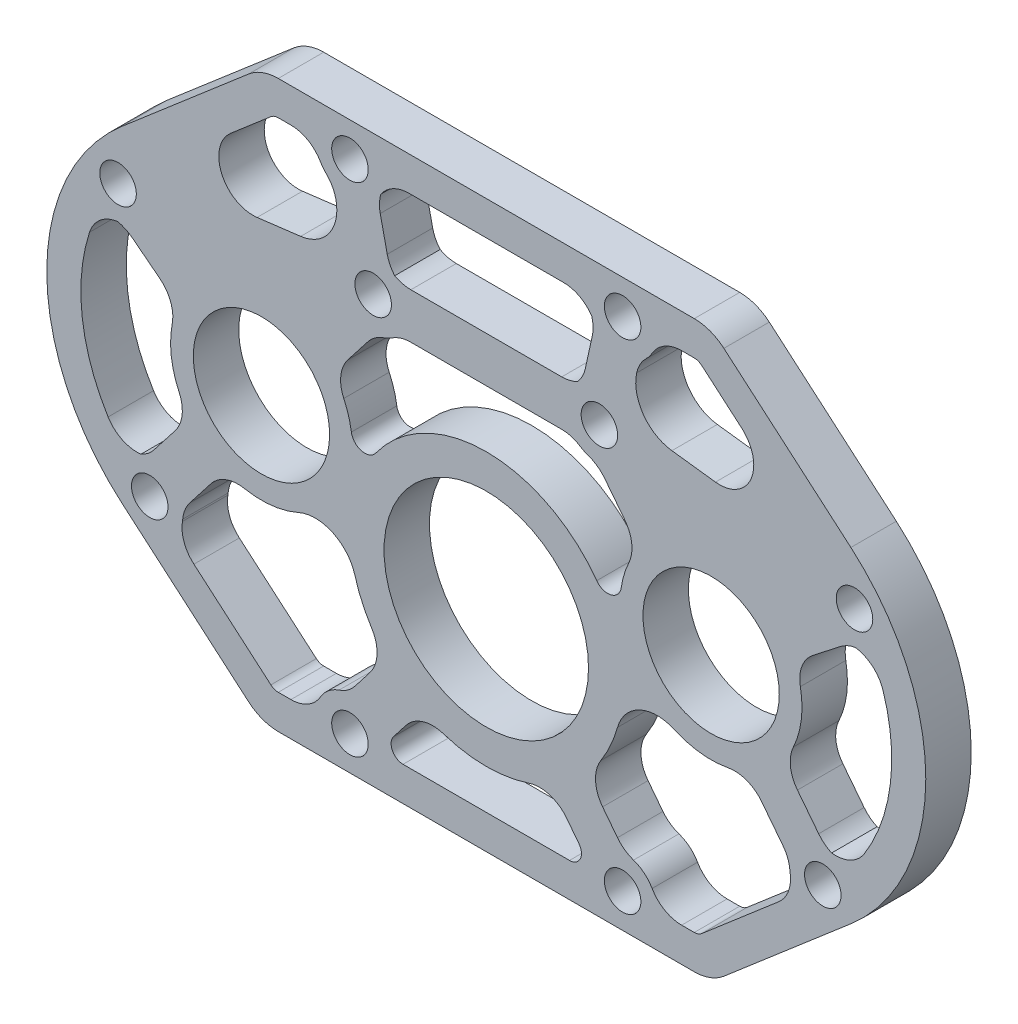
SolidWorks part; units mm, degrees
material "6061-T6 (SS)"
ref_plane "Front Plane" through (0, 0, 0) normal (0, 0, 1) x (1, 0, 0)
ref_plane "Top Plane" through (0, 0, 0) normal (0, 1, 0) x (1, 0, 0)
ref_plane "Right Plane" through (0, 0, 0) normal (1, 0, 0) x (0, 0, -1)
sketch "Sketch1" plane through (0, 0, 0) normal (0, 0, 1) x (1, 0, 0)
  line L0 (127, 25.4) -> (127, 0) construction
  line L1 (0, 0) -> (254, 0)
  line L2 (0, 0) -> (0, 25.4)
  line L3 (0, 25.4) -> (254, 25.4)
  line L4 (254, 0) -> (254, 25.4)
  line L18 (110.6338, 19.05) -> (106.9677, 12.7)
  line L19 (106.9677, 12.7) -> (110.6338, 6.35)
  line L20 (110.6338, 6.35) -> (117.9662, 6.35)
  line L21 (117.9662, 6.35) -> (121.6323, 12.7)
  line L22 (121.6323, 12.7) -> (117.9662, 19.05)
  line L23 (117.9662, 19.05) -> (110.6338, 19.05)
  circle A0 centre (82.8819, 22.86) radius 30 construction
  circle A1 centre (145.7181, 22.86) radius 30 construction
  circle A2 centre (82.8819, 22.86) radius 7.62 construction
  circle A3 centre (145.7181, 22.86) radius 8.636
  circle A4 centre (82.8819, 22.86) radius 8.636
  circle A5 centre (145.7181, 22.86) radius 7.62 construction
  circle A6 centre (114.3, 12.7) radius 25.4 construction
  circle A7 centre (114.3, 12.7) radius 26.67
  circle A8 centre (114.3, 12.7) radius 22.2377 construction
  circle A11 centre (114.3, 12.7) radius 6.35 construction
  dimension "D4" = 17.272
  dimension "D9" = 53.34
  dimension "D13" = 12.7
  dimension "D1" = 25.4
  dimension "D2" = 254
  dimension "D10" = 12.7
  dimension "D12" = 12.7
  dimension "D14" = 10.16
sketch "Sketch3" plane through (0, 0, 0) normal (0, 0, 1) x (1, 0, 0)
  line L0 (82.8819, 52.86) -> (145.7181, 52.86) construction
  line L5 (82.8819, -7.14) -> (145.7181, -7.14) construction
  line L6 (82.8819, 22.86) -> (98.4918, 42.8972) construction
  line L9 (114.3, 52.86) -> (114.3, -16.665) construction
  line L10 (63.3497, 45.6304) -> (82.8819, 62.385)
  line L25 (82.8819, 62.385) -> (145.7181, 62.385)
  line L26 (145.7181, 62.385) -> (165.2503, 45.6304)
  line L27 (110.6338, 19.05) -> (106.9677, 12.7)
  line L28 (106.9677, 12.7) -> (110.6338, 6.35)
  line L29 (110.6338, 6.35) -> (117.9662, 6.35)
  line L30 (117.9662, 6.35) -> (121.6323, 12.7)
  line L31 (121.6323, 12.7) -> (117.9662, 19.05)
  line L32 (117.9662, 19.05) -> (110.6338, 19.05)
  line L33 (110.565, 18.9308) -> (106.9677, 12.7)
  line L34 (106.9677, 12.7) -> (110.6338, 6.35)
  line L35 (110.6338, 6.35) -> (117.9662, 6.35)
  line L36 (117.9662, 6.35) -> (121.6323, 12.7)
  line L37 (121.6323, 12.7) -> (117.9662, 19.05)
  line L38 (117.9662, 19.05) -> (110.6338, 19.05)
  line L39 (96.3395, 30.6605) -> (132.2605, -5.2605) construction
  line L40 (82.8819, 22.86) -> (114.3, 12.7) construction
  line L41 (95.25, 57.6225) -> (133.35, 57.6225) construction
  line L43 (95.25, -11.9025) -> (133.35, -11.9025) construction
  line L44 (145.7181, -16.665) -> (165.2503, 0.0896)
  line L45 (82.8819, -16.665) -> (145.7181, -16.665)
  line L46 (63.3497, 0.0896) -> (82.8819, -16.665)
  line L47 (82.8819, 22.86) -> (67.272, 2.8228) construction
  line L48 (82.8819, 22.86) -> (67.272, 2.8228) construction
  line L49 (82.8819, 22.86) -> (62.8447, 38.4699) construction
  circle A2 centre (82.8819, 22.86) radius 30 construction
  circle A9 centre (114.3, 12.7) radius 26.67
  circle A10 centre (114.3, 12.7) radius 26.67 construction
  circle A11 centre (82.8819, 22.86) radius 8.636
  circle A12 centre (82.8819, 22.86) radius 8.636 construction
  circle A13 centre (145.7181, 22.86) radius 8.636
  circle A16 centre (145.7181, 22.86) radius 8.636 construction
  circle A17 centre (95.25, 57.6225) radius 2.5527
  circle A19 centre (114.3, 12.7) radius 25.4 construction
  circle A20 centre (114.3, 12.7) radius 22.2377 construction
  circle A22 centre (114.3, 12.7) radius 25.4 construction
  circle A23 centre (114.3, 12.7) radius 22.2377 construction
  arc A24 (112.6104, 26.8872) -> (104.6233, 2.1884) centre (82.8819, 22.86) ccw
  circle A25 centre (114.3, 12.7) radius 14.2875
  circle A26 centre (82.8819, 22.86) radius 9.525
  circle A27 centre (145.7181, 22.86) radius 9.525
  circle A37 centre (133.35, 57.6225) radius 2.5527
  circle A38 centre (133.35, -11.9025) radius 2.5527
  circle A39 centre (95.25, -11.9025) radius 2.5527
  circle A40 centre (67.272, 2.8228) radius 2.5527
  circle A41 centre (62.8447, 38.4699) radius 2.5527
  circle A42 centre (98.4918, 42.8972) radius 2.5527
  circle A43 centre (161.328, 2.8228) radius 2.5527
  circle A44 centre (165.7553, 38.4699) radius 2.5527
  circle A45 centre (130.1082, 42.8972) radius 2.5527
  circle A46 centre (95.25, -11.9025) radius 4.7625 construction
  arc A47 (123.9767, 2.1884) -> (115.9896, 26.8872) centre (145.7181, 22.86) ccw
  circle A48 centre (133.35, -11.9025) radius 4.7625 construction
  circle A49 centre (95.25, 57.6225) radius 4.7625 construction
  circle A50 centre (133.35, 57.6225) radius 4.7625 construction
  point P2 (114.3, 52.86)
  point P31 (114.3, -16.665)
  point P41 (114.3, 62.385)
  point P59 (114.3, 57.6225)
  point P60 (114.3, -11.9025)
  point P69 (114.3, 12.7)
  point P78 (82.8819, 22.86)
  point P84 (114.3, -22.0625)
  dimension "D3" = 70
  dimension "D4" = 9.525
  dimension "D2" = 45
  dimension "D8" = 25.4
  dimension "D14" = 28.575
  dimension "D15" = 19.05
  dimension "D16" = 3
  dimension "D5" = 5.1054
  dimension "D12" = 5.1054
  dimension "D7" = 4.7625
  dimension "D17" = 90
  dimension "2" = 50.8
  dimension "D6" = 19.05
  dimension "D9" = 0
  dimension "D10" = 0
  dimension "D11" = 0
  dimension "D13" = 0
extrude "Boss-Extrude1" add sketch "Sketch3" along normal blind 6.35 contours A24 A10 L26 L25 L10 A37 A17 | A24 L46 L45 L44 A10 A38 A39 | A10 A24 A12 A40 A42 | A23 A24 A25 | A23 A22 A12 | A22 A24 A10 A12 | A22 A12 A10 A24 | A24 A22 A23 | A24 A10 A22 | A22 A24 A23 | A25 A24 A23 | A25 A23 A24 | A24 A23 A22 | A24 A22 A10 | A23 A24 A22 | A23 A45 A25 A44 | A22 A45 A23 A44 A16 | A23 A45 A22 | A22 A45 A16 A10 | A10 A16 A43 | A22 A44 A23 | A22 A44 A10 A16 | A10 A26 A12 | A22 A12 A10 | A12 A22 | A10 A27 A16 | A16 A22 | A22 A16 A10 region at (87.3231, 51.7029, 0) region at (114.3, 53.784, 0) region at (77.9382, -7.7764, 0) region at (98.4388, 17.8292, 0) region at (114.3, 34.3639, 0) region at (114.3, -6.358, 0) region at (141.2769, 51.7029, 0) region at (130.1612, 17.8292, 0)
fillet "Fillet1" radius 6.35 4 edges at (145.7181, -16.665, 3.175) (82.8819, -16.665, 3.175) (145.7181, 62.385, 3.175) (82.8819, 62.385, 3.175)
sketch "Sketch4" plane through (0, 0, 6.35) normal (0, 0, 1) x (1, 0, 0)
  line L0 (85.2323, -11.9025) -> (143.3677, -11.9025)
  line L1 (144.4013, -11.5199) -> (162.1496, 3.7044)
  line L2 (162.1496, 42.0156) -> (144.4013, 57.2399)
  line L3 (143.3677, 57.6225) -> (85.2323, 57.6225)
  line L4 (84.1987, 57.2399) -> (66.4504, 42.0156)
  line L5 (66.4504, 3.7044) -> (84.1987, -11.5199)
  line L6 (85.2323, -16.665) -> (143.3677, -16.665)
  line L7 (147.502, -15.1347) -> (165.2503, 0.0896)
  line L8 (165.2503, 45.6304) -> (147.502, 60.8547)
  line L9 (143.3677, 62.385) -> (85.2323, 62.385)
  line L10 (81.098, 60.8547) -> (63.3497, 45.6304)
  line L11 (63.3497, 0.0896) -> (81.098, -15.1347)
  line L12 (85.2323, -16.665) -> (143.3677, -16.665)
  line L13 (147.502, -15.1347) -> (165.2503, 0.0896)
  line L14 (165.2503, 45.6304) -> (147.502, 60.8547)
  line L15 (143.3677, 62.385) -> (85.2323, 62.385)
  line L16 (81.098, 60.8547) -> (63.3497, 45.6304)
  line L17 (63.3497, 0.0896) -> (81.098, -15.1347)
  line L18 (95.25, 57.6225) -> (98.4918, 42.8972) construction
  line L19 (98.4918, 42.8972) -> (130.1082, 42.8972) construction
  line L20 (130.1082, 42.8972) -> (133.35, 57.6225) construction
  line L21 (82.8819, 22.86) -> (114.3, 12.7) construction
  line L22 (114.3, 12.7) -> (95.25, -11.9025) construction
  line L23 (62.8447, 38.4699) -> (82.8819, 22.86) construction
  line L24 (82.8819, 22.86) -> (67.272, 2.8228) construction
  line L25 (165.7553, 38.4699) -> (145.7181, 22.86) construction
  line L26 (145.7181, 22.86) -> (161.328, 2.8228) construction
  line L27 (114.3, 12.7) -> (133.35, -11.9025) construction
  line L28 (114.3, 12.7) -> (145.7181, 22.86) construction
  line L29 (98.4918, 42.8972) -> (82.8819, 22.86) construction
  line L30 (130.1082, 42.8972) -> (145.7181, 22.86) construction
  line L31 (62.8447, 38.4699) -> (98.4918, 42.8972) construction
  line L32 (130.1082, 42.8972) -> (165.7553, 38.4699) construction
  line L33 (129.7168, 39.7464) -> (157.7573, 36.2639)
  line L34 (157.7573, 36.2639) -> (143.7668, 25.3647)
  line L35 (92.1493, 56.9399) -> (95.3911, 42.2146)
  line L36 (133.2089, 42.2146) -> (136.4507, 56.9399)
  line L37 (98.4918, 39.7222) -> (130.1082, 39.7222)
  line L38 (95.9872, 44.8485) -> (80.3773, 24.8112)
  line L39 (70.8427, 36.2639) -> (84.8332, 25.3647)
  line L40 (70.8427, 36.2639) -> (98.8832, 39.7464)
  line L41 (80.3773, 24.8112) -> (64.7674, 4.774)
  line L42 (81.905, 19.839) -> (113.3231, 9.679)
  line L43 (111.7896, 14.6438) -> (92.7396, -9.9587)
  line L44 (115.2769, 9.679) -> (146.695, 19.839)
  line L45 (111.7896, 10.7562) -> (130.8396, -13.8463)
  line L46 (143.2134, 20.9088) -> (158.8233, 0.8715)
  line L47 (127.6035, 40.946) -> (143.2134, 20.9088)
  line L48 (130.4995, 46.048) -> (169.4513, 41.2103)
  line L49 (171.2024, 38.6887) -> (147.6693, 20.3553)
  line L50 (98.3507, 58.3051) -> (101.5926, 43.5799)
  line L51 (127.0074, 43.5799) -> (130.2493, 58.3051)
  line L52 (98.4918, 46.0722) -> (130.1082, 46.0722)
  line L53 (100.9965, 40.946) -> (85.3866, 20.9088)
  line L54 (57.3976, 38.6887) -> (80.9307, 20.3553)
  line L55 (59.1487, 41.2103) -> (98.1005, 46.048)
  line L56 (85.3866, 20.9088) -> (69.7767, 0.8715)
  line L57 (83.8589, 25.881) -> (115.2769, 15.721)
  line L58 (116.8104, 10.7562) -> (97.7604, -13.8463)
  line L59 (113.3231, 15.721) -> (144.7411, 25.881)
  line L60 (116.8104, 14.6438) -> (135.8604, -9.9587)
  line L61 (148.2227, 24.8112) -> (163.8326, 4.774)
  line L62 (132.6128, 44.8485) -> (148.2227, 24.8112)
  line L63 (54.8467, 40.676) -> (98.1005, 46.048) construction
  line L64 (54.8467, 40.676) -> (80.9307, 20.3553) construction
  line L65 (130.4995, 46.048) -> (173.7533, 40.676) construction
  line L66 (173.7533, 40.676) -> (147.6693, 20.3553) construction
  arc A0 (143.3677, -11.9025) -> (144.4013, -11.5199) centre (143.3677, -10.315) ccw
  arc A1 (162.1496, 3.7044) -> (162.1496, 42.0156) centre (145.7181, 22.86) ccw
  arc A2 (144.4013, 57.2399) -> (143.3677, 57.6225) centre (143.3677, 56.035) ccw
  arc A3 (85.2323, 57.6225) -> (84.1987, 57.2399) centre (85.2323, 56.035) ccw
  arc A4 (66.4504, 42.0156) -> (66.4504, 3.7044) centre (82.8819, 22.86) ccw
  arc A5 (84.1987, -11.5199) -> (85.2323, -11.9025) centre (85.2323, -10.315) ccw
  arc A6 (143.3677, -16.665) -> (147.502, -15.1347) centre (143.3677, -10.315) ccw
  arc A7 (165.2503, 0.0896) -> (165.2503, 45.6304) centre (145.7181, 22.86) ccw
  arc A8 (147.502, 60.8547) -> (143.3677, 62.385) centre (143.3677, 56.035) ccw
  arc A9 (85.2323, 62.385) -> (81.098, 60.8547) centre (85.2323, 56.035) ccw
  arc A10 (63.3497, 45.6304) -> (63.3497, 0.0896) centre (82.8819, 22.86) ccw
  arc A11 (81.098, -15.1347) -> (85.2323, -16.665) centre (85.2323, -10.315) ccw
  arc A12 (143.3677, -16.665) -> (147.502, -15.1347) centre (143.3677, -10.315) ccw
  arc A13 (165.2503, 0.0896) -> (165.2503, 45.6304) centre (145.7181, 22.86) ccw
  arc A14 (147.502, 60.8547) -> (143.3677, 62.385) centre (143.3677, 56.035) ccw
  arc A15 (85.2323, 62.385) -> (81.098, 60.8547) centre (85.2323, 56.035) ccw
  arc A16 (63.3497, 45.6304) -> (63.3497, 0.0896) centre (82.8819, 22.86) ccw
  arc A17 (81.098, -15.1347) -> (85.2323, -16.665) centre (85.2323, -10.315) ccw
  circle A18 centre (95.25, 57.6225) radius 4.7625
  circle A19 centre (133.35, 57.6225) radius 4.7625
  circle A20 centre (95.25, -11.9025) radius 4.7625
  circle A21 centre (133.35, -11.9025) radius 4.7625
  circle A22 centre (161.328, 2.8228) radius 4.6282
  circle A23 centre (67.272, 2.8228) radius 4.6282
  circle A24 centre (62.8447, 38.4699) radius 4.6
  circle A25 centre (165.7553, 38.4699) radius 4.6
  circle A26 centre (98.4918, 42.8972) radius 4.7625
  circle A27 centre (130.1082, 42.8972) radius 4.7625
  circle A28 centre (114.3, 12.7) radius 19.05
  circle A29 centre (82.8819, 22.86) radius 12.7
  circle A30 centre (145.7181, 22.86) radius 12.7
  dimension "D3" = 38.1
  dimension "D4" = 25.4
  dimension "D5" = 3.175
  dimension "D1" = 0
  dimension "D2" = 4.7625
  dimension "D6" = 3.175
extrude "Cut-Extrude1" cut sketch "Sketch4" against normal up to surface (6.35 mm away) contours A29 L54 A24 A4 A23 L41 | A26 L35 A18 L3 A3 L4 L55 | A27 L51 A19 L3 A18 L50 A26 L52 | A27 L48 L2 A2 L3 A19 L36 | A30 L61 A22 A1 A25 L49 | A30 L44 A28 L60 A21 L0 A0 L1 A22 L46 | A28 L58 A20 L0 A21 L45 | A29 L56 A23 L5 A5 L0 A20 L43 A28 L42 | A30 L47 A27 L37 A26 L53 A29 L57 A28 L59 region at (142.4926, 1.1618, 6.35) region at (114.3, -8.8828, 6.35) region at (86.1074, 1.1618, 6.35) region at (164.1412, 20.5761, 6.35) region at (114.3, 32.9152, 6.35) region at (64.4588, 20.5761, 6.35) region at (145.2048, 49.2972, 6.35) region at (114.3, 51.9634, 6.35) region at (83.3952, 49.2972, 6.35) up to face at (114.3, 22.86, 0)
fillet "Fillet2" radius 4.7625 50 edges at (66.5888, 42.1343, 3.175) (92.9125, 53.4731, 3.175) (90.4875, 57.6225, 3.175) (72.8202, 15.1108, 3.175) (66.8369, 7.4305, 3.175) (64.0088, 6.1048, 3.175) (60.4965, 34.5144, 3.175) (63.5193, 33.9196, 3.175) (71.2302, 27.9125, 3.175) (128.5875, -11.9025, 3.175) (100.0125, -11.9025, 3.175) (105.3105, -4.0956, 3.175) (123.2895, -4.0956, 3.175) (100.2897, -0.2079, 3.175) (94.9129, -7.1519, 3.175) (90.4875, -11.9025, 3.175) (70.8709, -0.0874, 3.175) (71.8462, 3.528, 3.175) (77.8295, 11.2083, 3.175) (150.7705, 11.2083, 3.175) (157.7291, -0.0874, 3.175) (138.1125, -11.9025, 3.175) (133.6871, -7.1519, 3.175) (128.3103, -0.2079, 3.175) (156.7538, 3.528, 3.175) (157.3698, 27.9125, 3.175) (165.0807, 33.9196, 3.175) (164.5912, 6.1048, 3.175) (161.7631, 7.4305, 3.175) (155.7798, 15.1108, 3.175) (168.1035, 34.5144, 3.175) (126.5584, 46.0722, 3.175) (102.0416, 46.0722, 3.175) (100.8294, 47.0466, 3.175) (99.114, 54.8384, 3.175) (100.0125, 57.6225, 3.175) (129.486, 54.8384, 3.175) (127.7706, 47.0466, 3.175) (128.5875, 57.6225, 3.175) (135.6875, 53.4731, 3.175) (138.1125, 57.6225, 3.175) (162.0112, 42.1343, 3.175) (135.6563, 30.6092, 3.175) (92.9437, 30.6092, 3.175) (102.0416, 39.7222, 3.175) (126.5584, 39.7222, 3.175) (129.785, 38.1457, 3.175) (98.815, 38.1457, 3.175) (95.559, 22.0974, 3.175) (133.041, 22.0974, 3.175)
sketch "Sketch6" plane through (0, 0, 0) normal (0, 0, -1) x (-1, 0, 0)
  line L0 (-125.9324, -11.9025) -> (-102.6676, -11.9025) construction
  line L1 (-94.5778, 45.6105) -> (-88.3626, 44.8386)
  line L2 (-95.4508, 15.4586) -> (-93.6052, 16.0554) construction
  line L3 (-134.9948, 16.0554) -> (-133.1492, 15.4586) construction
  line L4 (-95.4508, 15.4586) -> (-93.6052, 16.0554)
  line L5 (-134.9948, 16.0554) -> (-133.1492, 15.4586)
  line L10 (-128.6663, -11.0396) -> (-125.5346, -6.9951) construction
  line L12 (-135.3187, 51.7979) -> (-133.9721, 45.6813) construction
  line L13 (-146.3291, 44.082) -> (-134.0222, 45.6105) construction
  line L14 (-94.5778, 45.6105) -> (-82.2709, 44.082) construction
  line L15 (-94.6279, 45.6813) -> (-93.2813, 51.7979) construction
  line L16 (-99.9337, -11.0396) -> (-103.0654, -6.9951) construction
  line L17 (-128.6663, -11.0396) -> (-127.2516, -9.2126)
  line L18 (-135.3187, 51.7979) -> (-133.9721, 45.6813)
  line L19 (-140.2374, 44.8386) -> (-134.0222, 45.6105)
  line L21 (-94.6279, 45.6813) -> (-93.2813, 51.7979)
  line L22 (-99.9337, -11.0396) -> (-101.3484, -9.2126)
  arc A0 (-135.3187, 51.7979) -> (-140.2374, 44.8386) centre (-140.9478, 50.5586) cw
  arc A1 (-97.4046, 21.5005) -> (-95.4485, 24.6959) centre (-100.161, 25.3843) ccw
  arc A2 (-93.2813, 51.7979) -> (-88.3626, 44.8386) centre (-87.6522, 50.5586) ccw
  arc A3 (-127.2516, -9.2126) -> (-125.9324, -11.9025) centre (-125.9324, -10.234) ccw
  arc A4 (-97.4046, 21.5005) -> (-98.8607, 23.8594) centre (-114.3, 12.7) ccw
  arc A5 (-101.3484, -9.2126) -> (-102.6676, -11.9025) centre (-102.6676, -10.234) cw
  arc A6 (-135.3187, 51.7979) -> (-136.6599, 54.1982) centre (-139.9698, 50.7739) ccw construction
  arc A7 (-94.5778, 45.6105) -> (-94.6279, 45.6813) centre (-98.4918, 42.8972) ccw construction
  arc A8 (-102.6676, -11.9025) -> (-99.9337, -11.0396) centre (-102.6676, -7.14) ccw construction
  arc A9 (-128.6663, -11.0396) -> (-125.9324, -11.9025) centre (-125.9324, -7.14) ccw construction
  arc A10 (-102.6676, -11.9025) -> (-99.9337, -11.0396) centre (-102.6676, -7.14) ccw
  arc A11 (-128.6663, -11.0396) -> (-125.9324, -11.9025) centre (-125.9324, -7.14) ccw
  arc A12 (-133.9721, 45.6813) -> (-134.0222, 45.6105) centre (-130.1082, 42.8972) ccw construction
  arc A13 (-94.5778, 45.6105) -> (-94.6279, 45.6813) centre (-98.4918, 42.8972) ccw
  arc A14 (-133.9721, 45.6813) -> (-134.0222, 45.6105) centre (-130.1082, 42.8972) ccw
  arc A15 (-140.5415, 11.2629) -> (-132.6423, 7.5559) centre (-138.1921, 5.9995) cw
  arc A16 (-148.1162, 10.3885) -> (-134.9948, 16.0554) centre (-145.7181, 22.86) ccw construction
  arc A17 (-133.1492, 15.4586) -> (-130.3168, 2.3867) centre (-114.3, 12.7) ccw construction
  arc A18 (-95.9577, 7.5559) -> (-88.0585, 11.2629) centre (-90.4079, 5.9995) cw
  arc A19 (-98.2832, 2.3867) -> (-95.4508, 15.4586) centre (-114.3, 12.7) ccw construction
  arc A20 (-93.6052, 16.0554) -> (-80.4838, 10.3885) centre (-82.8819, 22.86) ccw construction
  arc A21 (-93.6052, 16.0554) -> (-88.0585, 11.2629) centre (-82.8819, 22.86) ccw
  arc A22 (-95.9577, 7.5559) -> (-95.4508, 15.4586) centre (-114.3, 12.7) ccw
  arc A23 (-133.1492, 15.4586) -> (-132.6423, 7.5559) centre (-114.3, 12.7) ccw
  arc A24 (-140.5415, 11.2629) -> (-134.9948, 16.0554) centre (-145.7181, 22.86) ccw
  arc A25 (-133.1515, 24.6959) -> (-129.7393, 23.8594) centre (-131.2757, 24.9699) ccw
  arc A26 (-133.1515, 24.6959) -> (-131.1954, 21.5005) centre (-128.439, 25.3843) ccw construction
  arc A27 (-97.4046, 21.5005) -> (-131.1954, 21.5005) centre (-114.3, 12.7) ccw construction
  arc A28 (-95.4485, 24.6959) -> (-98.8607, 23.8594) centre (-97.3243, 24.9699) cw
  arc A29 (-97.4046, 21.5005) -> (-95.4485, 24.6959) centre (-100.161, 25.3843) ccw construction
  arc A30 (-133.1515, 24.6959) -> (-131.1954, 21.5005) centre (-128.439, 25.3843) ccw
  arc A31 (-129.7393, 23.8594) -> (-131.1954, 21.5005) centre (-114.3, 12.7) ccw
  point P61 (-128.485, 25.4157)
  point P65 (-130.1763, 23.2284)
  point P66 (0, 0)
  point P68 (0, 0)
extrude "Boss-Extrude2" add sketch "Sketch6" against normal up to surface (6.35 mm away) up to face at (114.3, 22.86, 6.35)
equation "\"NEO\"= 60mm"
equation "\"D3@Sketch1\"=\"NEO\""
equation "\"D5@Sketch1\"=\"NEO\""
